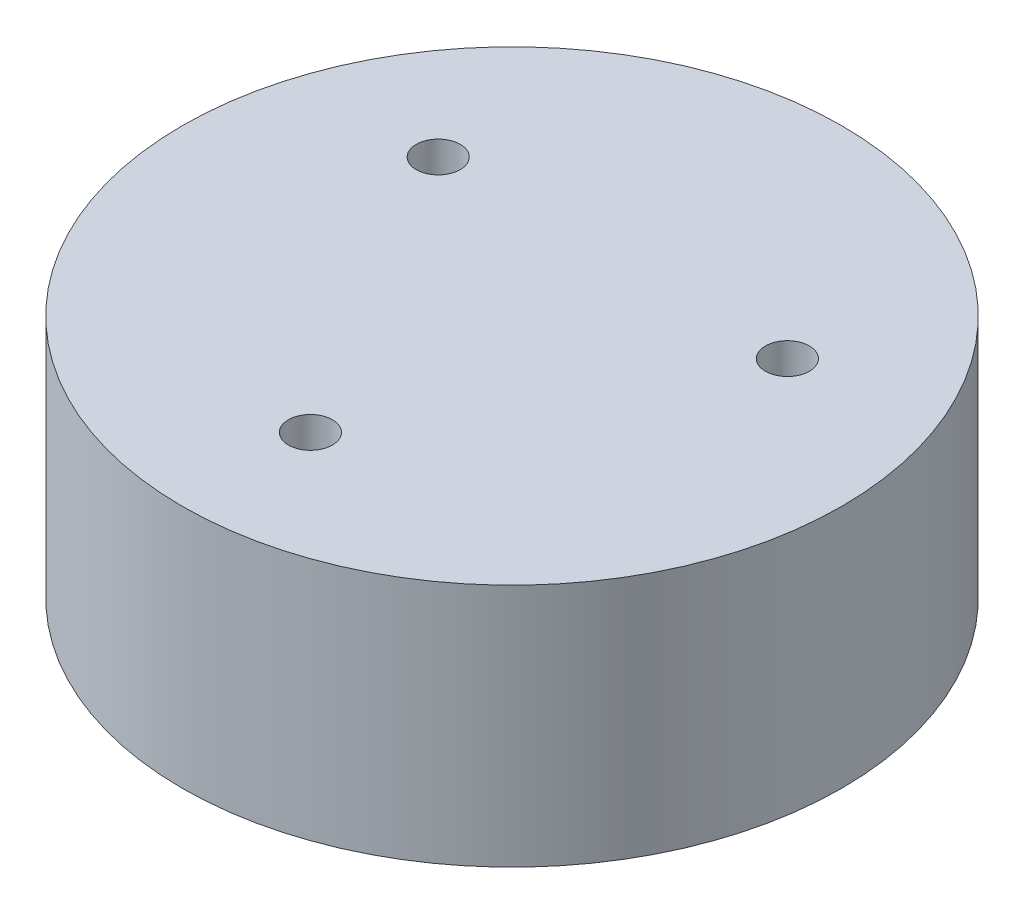
SolidWorks part; units mm, degrees
ref_plane "Front Plane" through (0, 0, 0) normal (0, 0, 1) x (1, 0, 0)
ref_plane "Top Plane" through (0, 0, 0) normal (0, 1, 0) x (1, 0, 0)
ref_plane "Right Plane" through (0, 0, 0) normal (1, 0, 0) x (0, 0, -1)
sketch "Sketch2" plane through (0, 0, 0) normal (0, 1, 0) x (1, 0, 0)
  circle A0 centre (0, 0) radius 27
  dimension "D1" = 54
extrude "Boss-Extrude2" add sketch "Sketch2" along normal blind 20
sketch "Sketch6" plane through (0, 0, 0) normal (0, -1, 0) x (-1, 0, 0)
  line L0 (-14.2981, 8.255) -> (0, 0) construction
  line L1 (0, 0) -> (14.2981, 8.255) construction
  line L3 (0, 0) -> (0, -16.51) construction
  point P0 (0, -16.51)
  point P2 (-14.2981, 8.255)
  point P4 (14.2981, 8.255)
  dimension "D1" = 16.51
  dimension "D2" = 120
  dimension "D3" = 120
hole_wizard "CBORE for M3 SHCS1" positions "Sketch6" profile "Sketch5" counterbore size "M3" standard "ANSI Metric" end condition through all
sketch "Sketch5" plane through (0, 0, 16.51) normal (1, 0, 0) x (0, 0, -1)
  line L0 (0, 0) -> (0, 20)
  line L1 (0, 20) -> (1.8, 20)
  line L3 (1.8, 20) -> (1.8, 16)
  line L4 (3.25, 16) -> (1.8, 16)
  line L5 (3.25, 16) -> (3.25, 0.025)
  line L6 (3.25, 0.025) -> (3.275, 0)
  line L7 (3.275, 0) -> (0, 0)
  line L8 (-3.25, 0.025) -> (-3.275, 0) construction
  line L11 (0, -6.35) -> (0, 107.95) construction
  dimension "Thru Hole Dia." = 3.6
  dimension "Thru Hole Depth" = 20
  dimension "C'Bore Dia." = 6.5
  dimension "C'Bore Depth" = 16
  dimension "Near C'Sink Dia." = 6.55
  dimension "Near C'Sink Angle" = 90
sketch "Sketch9" plane through (0, 0, 0) normal (0, -1, 0) x (-1, 0, 0)
  line L0 (-14.2981, -8.255) -> (0, 0) construction
  line L1 (0, 0) -> (0, 16.51) construction
  line L2 (0, 0) -> (14.2981, -8.255) construction
  point P0 (14.2981, -8.255)
  point P2 (0, 16.51)
  point P4 (-14.2981, -8.255)
  dimension "D1" = 120
  dimension "D2" = 120
  dimension "D3" = 16.51
hole_wizard "Hole1" positions "Sketch9" profile "Sketch8" legacy
sketch "Sketch8" plane through (-14.2981, 0, 8.255) normal (1, 0, 0) x (0, 0, -1)
  line L0 (0, 0) -> (0, 15)
  line L1 (0, 15) -> (3.2, 15)
  line L2 (3.2, 15) -> (3.2, 2)
  line L3 (3.2, 2) -> (3.65, 2)
  line L4 (3.65, 2) -> (3.65, 0)
  line L5 (3.65, 0) -> (0, 0)
  line L6 (0, 110) -> (0, -10) construction
  dimension "Diameter" = 6.4
  dimension "Depth" = 15
  dimension "C-Bore Diameter" = 7.3
  dimension "C-Bore Depth" = 2
chamfer "Chamfer1" distance 2 distance2 0.45 3 edges at (-14.2981, 2, 4.605) (0, 2, -20.16) (14.2981, 2, 4.605) first distance on face at (-14.2981, 2, 4.605) first distance on face at (0, 2, -20.16) first distance on face at (14.2981, 2, 4.605)
